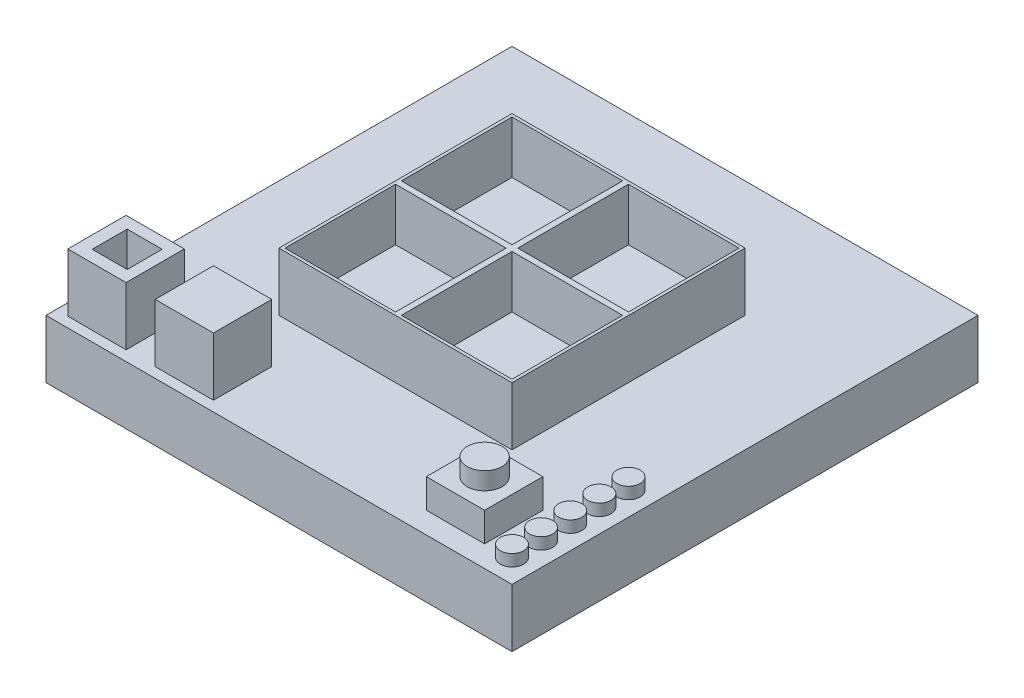
SolidWorks part; units mm, degrees
ref_plane "Front Plane" through (0, 0, 0) normal (0, 0, 1) x (1, 0, 0)
ref_plane "Top Plane" through (0, 0, 0) normal (0, 1, 0) x (1, 0, 0)
ref_plane "Right Plane" through (0, 0, 0) normal (1, 0, 0) x (0, 0, -1)
sketch "Sketch1" plane through (0, 0, 0) normal (0, 1, 0) x (1, 0, 0)
  line L1 (-200, 200) -> (200, 200)
  line L2 (-200, 200) -> (-200, -200)
  line L3 (-200, -200) -> (200, -200)
  line L4 (200, 200) -> (200, -200)
  line L5 (-200, 200) -> (200, -200) construction
  line L6 (-200, -200) -> (200, 200) construction
  point P0 (0, 0)
  dimension "D1" = 400
  dimension "D2" = 400
extrude "Boss-Extrude1" add sketch "Sketch1" along normal blind 50 contours L3 L4 L1 L2
sketch "Sketch3" plane through (0, 50, 0) normal (0, 1, 0) x (1, 0, 0)
  line L1 (-100, 100) -> (100, 100)
  line L2 (-100, 100) -> (-100, -100)
  line L3 (-100, -100) -> (100, -100)
  line L4 (100, 100) -> (100, -100)
  line L5 (-100, 100) -> (100, -100) construction
  line L6 (-100, -100) -> (100, 100) construction
  point P0 (0, 0)
  dimension "D1" = 200
  dimension "D2" = 200
extrude "Boss-Extrude2" add sketch "Sketch3" along normal blind 50
sketch "Sketch4" plane through (0, 100, 0) normal (0, 1, 0) x (1, 0, 0)
  line L0 (-100, 0) -> (100, 0) construction
  line L1 (-100, 100) -> (-100, -100) construction
  line L2 (100, -100) -> (100, 100) construction
  line L3 (0, 100) -> (0, -100) construction
  line L4 (100, 100) -> (-100, 100) construction
  line L5 (-100, -100) -> (100, -100) construction
  line L6 (0, 0) -> (100, 100) construction
  line L7 (-100, 100) -> (0, 0) construction
  line L8 (-100, -100) -> (0, 0) construction
  line L9 (0, 0) -> (100, -100) construction
  line L11 (-97.5, -2.5) -> (-2.5, -2.5)
  line L12 (-97.5, -2.5) -> (-97.5, -97.5)
  line L13 (-97.5, -97.5) -> (-2.5, -97.5)
  line L14 (-2.5, -2.5) -> (-2.5, -97.5)
  line L15 (-97.5, -2.5) -> (-2.5, -97.5) construction
  line L16 (-97.5, -97.5) -> (-2.5, -2.5) construction
  line L17 (2.5, -2.5) -> (97.5, -2.5)
  line L18 (2.5, -2.5) -> (2.5, -97.5)
  line L19 (2.5, -97.5) -> (97.5, -97.5)
  line L20 (97.5, -2.5) -> (97.5, -97.5)
  line L21 (2.5, -2.5) -> (97.5, -97.5) construction
  line L22 (2.5, -97.5) -> (97.5, -2.5) construction
  line L23 (-97.5, 97.5) -> (-2.5, 97.5)
  line L24 (-97.5, 97.5) -> (-97.5, 2.5)
  line L25 (-97.5, 2.5) -> (-2.5, 2.5)
  line L26 (-2.5, 97.5) -> (-2.5, 2.5)
  line L27 (-97.5, 97.5) -> (-2.5, 2.5) construction
  line L28 (-97.5, 2.5) -> (-2.5, 97.5) construction
  line L29 (2.5, 97.5) -> (97.5, 97.5)
  line L30 (2.5, 97.5) -> (2.5, 2.5)
  line L31 (2.5, 2.5) -> (97.5, 2.5)
  line L32 (97.5, 97.5) -> (97.5, 2.5)
  line L33 (2.5, 97.5) -> (97.5, 2.5) construction
  line L34 (2.5, 2.5) -> (97.5, 97.5) construction
  point P22 (-50, -50)
  point P27 (50, -50)
  point P32 (-50, 50)
  point P37 (50, 50)
  dimension "D1" = 95
  dimension "D2" = 95
  dimension "D3" = 95
  dimension "D4" = 95
  dimension "D5" = 95
extrude "Cut-Extrude1" cut sketch "Sketch4" against normal blind 45
ref_axis "Axis1" through (0, 0, 220) along (0, 0, -1)
sketch "Sketch6" plane through (0, 50, 0) normal (0, 1, 0) x (1, 0, 0)
  line L0 (200, -200) -> (180, -200) construction
  line L1 (-200, -200) -> (200, -200) construction
  line L2 (200, -200) -> (200, -180) construction
  line L3 (200, 200) -> (200, -200) construction
  circle A0 centre (180, -180) radius 10
  dimension "D1" = 20
  dimension "D2" = 20
extrude "Boss-Extrude4" add sketch "Sketch6" along normal blind 10
pattern_linear "LPattern3" count 5 spacing 25 along (0, 0, -1) of "Boss-Extrude4"
sketch "Sketch7" plane through (0, 50, 0) normal (0, 1, 0) x (1, 0, 0)
  line L1 (108.1179, -131.6305) -> (158.1179, -131.6305)
  line L2 (108.1179, -131.6305) -> (108.1179, -181.6305)
  line L3 (108.1179, -181.6305) -> (158.1179, -181.6305)
  line L4 (158.1179, -131.6305) -> (158.1179, -181.6305)
  line L5 (108.1179, -131.6305) -> (158.1179, -181.6305) construction
  line L6 (108.1179, -181.6305) -> (158.1179, -131.6305) construction
  point P0 (133.1179, -156.6305)
  dimension "D1" = 50
  dimension "D2" = 50
extrude "Boss-Extrude5" add sketch "Sketch7" along normal blind 25
sketch "Sketch8" plane through (0, 75, 0) normal (0, 1, 0) x (1, 0, 0)
  circle A0 centre (133.1179, -156.6305) radius 15
  dimension "D1" = 30
extrude "Boss-Extrude6" add sketch "Sketch8" along normal blind 15
sketch "Sketch10" plane through (0, 50, 0) normal (0, 1, 0) x (1, 0, 0)
  line L0 (-200, -200) -> (-165, -200) construction
  line L1 (-200, -200) -> (200, -200) construction
  line L2 (-200, -200) -> (-200, -165) construction
  line L3 (-200, 200) -> (-200, -200) construction
  line L5 (-190.0228, -141.2453) -> (-140.0228, -141.2453)
  line L6 (-190.0228, -141.2453) -> (-190.0228, -191.2453)
  line L7 (-190.0228, -191.2453) -> (-140.0228, -191.2453)
  line L8 (-140.0228, -141.2453) -> (-140.0228, -191.2453)
  line L9 (-190.0228, -141.2453) -> (-140.0228, -191.2453) construction
  line L10 (-190.0228, -191.2453) -> (-140.0228, -141.2453) construction
  point P5 (-165.0228, -166.2453)
  dimension "D1" = 35
  dimension "D2" = 35
  dimension "D3" = 50
  dimension "D4" = 50
extrude "Boss-Extrude7" add sketch "Sketch10" along normal blind 50
sketch "Sketch12" plane through (0, 100, 0) normal (0, 1, 0) x (1, 0, 0)
  line L1 (-179.2769, -151.0254) -> (-149.2769, -151.0254)
  line L2 (-179.2769, -151.0254) -> (-179.2769, -181.0254)
  line L3 (-179.2769, -181.0254) -> (-149.2769, -181.0254)
  line L4 (-149.2769, -151.0254) -> (-149.2769, -181.0254)
  line L5 (-179.2769, -151.0254) -> (-149.2769, -181.0254) construction
  line L6 (-179.2769, -181.0254) -> (-149.2769, -151.0254) construction
  point P0 (-164.2769, -166.0254)
  dimension "D1" = 30
  dimension "D2" = 30
extrude "Cut-Extrude2" cut sketch "Sketch12" against normal blind 45
sketch "Sketch13" plane through (0, 50, 0) normal (0, 1, 0) x (1, 0, 0)
  line L0 (-140.0228, -166.2453) -> (-90.0228, -166.2453) construction
  line L1 (-140.0228, -191.2453) -> (-140.0228, -141.2453) construction
  line L3 (-115.0228, -141.2453) -> (-65.0228, -141.2453)
  line L4 (-115.0228, -141.2453) -> (-115.0228, -191.2453)
  line L5 (-115.0228, -191.2453) -> (-65.0228, -191.2453)
  line L6 (-65.0228, -141.2453) -> (-65.0228, -191.2453)
  line L7 (-115.0228, -141.2453) -> (-65.0228, -191.2453) construction
  line L8 (-115.0228, -191.2453) -> (-65.0228, -141.2453) construction
  dimension "D1" = 50
  dimension "D2" = 50
  dimension "D3" = 50
extrude "Boss-Extrude8" add sketch "Sketch13" along normal blind 50
